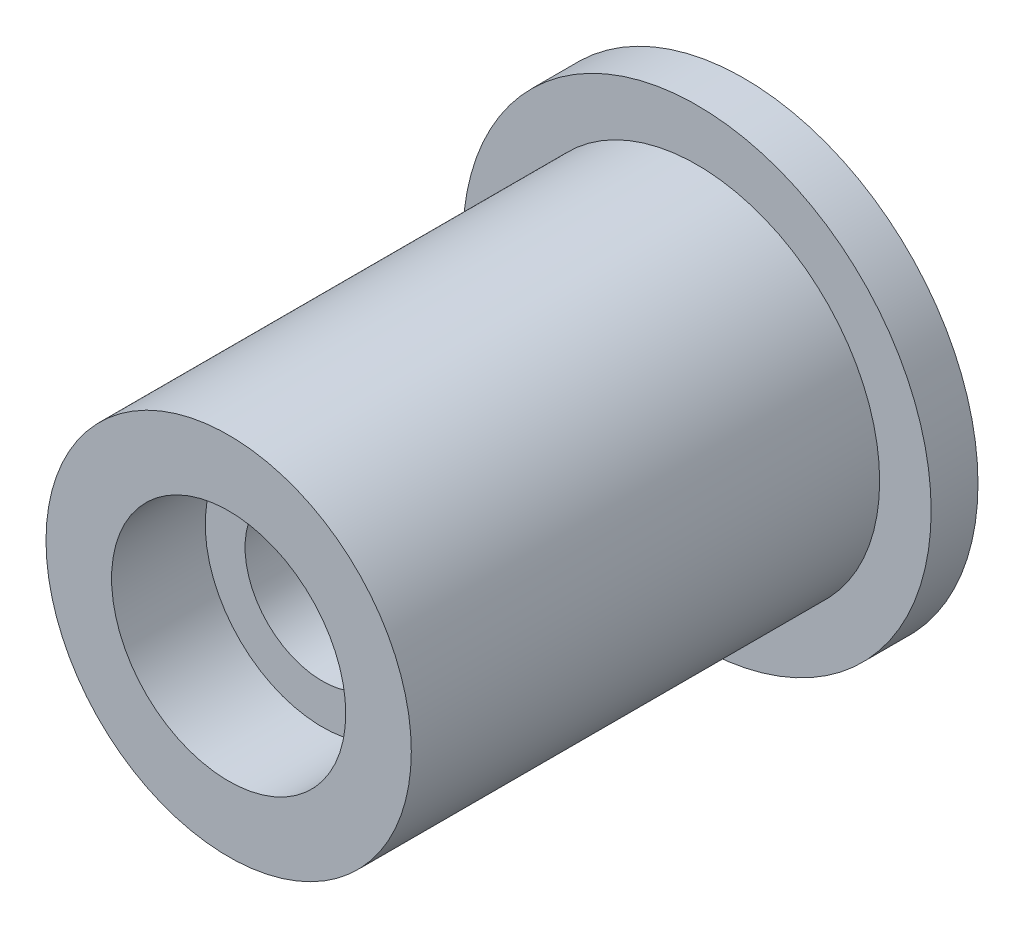
SolidWorks part; units mm, degrees
ref_plane "Front Plane" through (0, 0, 0) normal (0, 0, 1) x (1, 0, 0)
ref_plane "Top Plane" through (0, 0, 0) normal (0, 1, 0) x (1, 0, 0)
ref_plane "Right Plane" through (0, 0, 0) normal (1, 0, 0) x (0, 0, -1)
ref_axis "X" through (-88.99, 0, 0) along (1, 0, 0)
ref_axis "Y" through (0, 55, 0) along (0, -1, 0)
ref_axis "Z" through (0, 0, -88.99) along (0, 0, 1)
sketch "Sketch1" plane through (0, 0, 0) normal (0, 0, 1) x (1, 0, 0)
  circle A0 centre (0, 0) radius 3.9
  circle A1 centre (0, 0) radius 1.65
  circle A2 centre (0, 0) radius 2.5
  circle A3 centre (0, 0) radius 5
  dimension "D1" = 7.8
  dimension "D2" = 3.3
  dimension "D3" = 5
  dimension "D4" = 10
extrude "Boss-Extrude1" add sketch "Sketch1" against normal blind 1 contours A3 | A1
extrude "Boss-Extrude2" add sketch "Sketch1<3>" along normal blind 10 contours A0 A2 region at (-3.7897, 0, 0)
sketch "Sketch1<3>" plane through (0, 0, 0) normal (0, 0, 1) x (1, 0, 0) same geometry as "Sketch1"
extrude "Boss-Extrude3" add sketch "Sketch1<4>" along normal blind 8 contours A2 A1 region at (-2.4293, 0, 0)
sketch "Sketch1<4>" plane through (0, 0, 0) normal (0, 0, 1) x (1, 0, 0) same geometry as "Sketch1"
